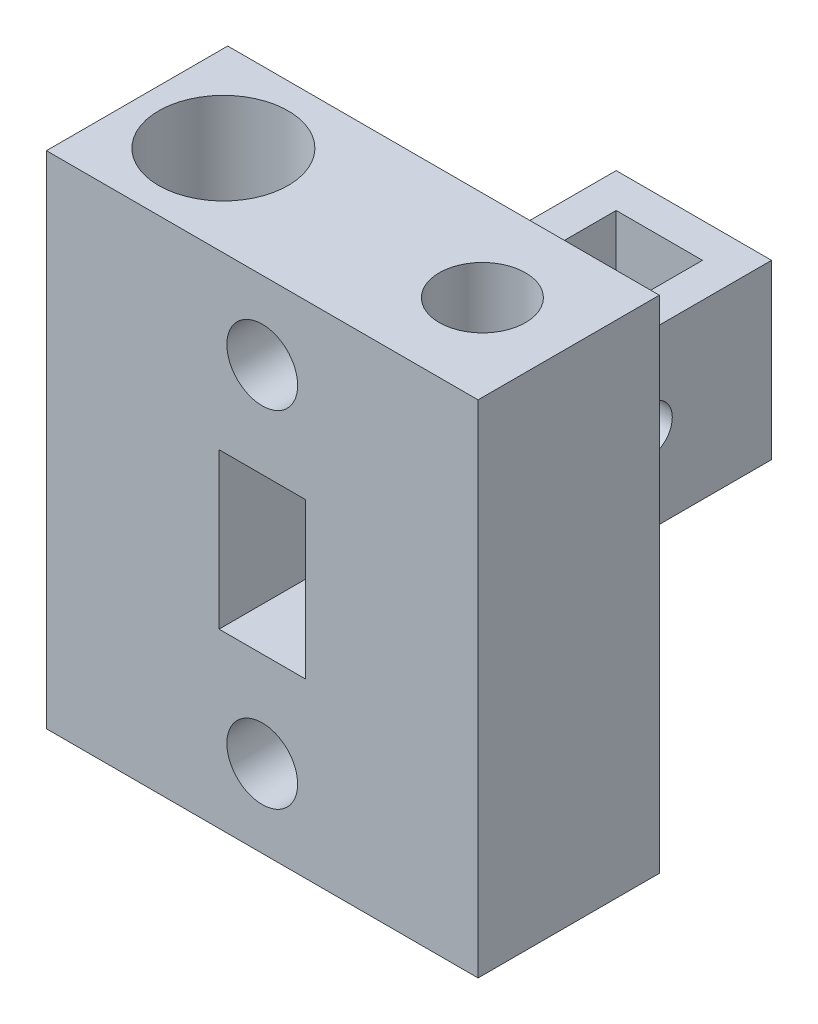
SolidWorks part; units mm, degrees
ref_plane "Front Plane" through (0, 0, 0) normal (0, 0, 1) x (1, 0, 0)
ref_plane "Top Plane" through (0, 0, 0) normal (0, 1, 0) x (1, 0, 0)
ref_plane "Right Plane" through (0, 0, 0) normal (1, 0, 0) x (0, 0, -1)
sketch "Sketch1" plane through (0, 0, 0) normal (0, 1, 0) x (1, 0, 0)
  line L1 (-25, 10.5) -> (25, 10.5)
  line L2 (-25, 10.5) -> (-25, -10.5)
  line L3 (-25, -10.5) -> (25, -10.5)
  line L4 (25, 10.5) -> (25, -10.5)
  line L5 (-25, 10.5) -> (25, -10.5) construction
  line L6 (-25, -10.5) -> (25, 10.5) construction
  point P0 (0, 0)
  dimension "D1" = 21
  dimension "D2" = 50
extrude "Boss-Extrude1" add sketch "Sketch1" along normal blind 58
sketch "Sketch3" plane through (0, 58, 0) normal (0, 1, 0) x (1, 0, 0)
  line L0 (-15, 0) -> (15, 0) construction
  circle A0 centre (-15, 0) radius 7.5
  dimension "D1" = 15
  dimension "D2" = 30
extrude "Cut-Extrude1" cut sketch "Sketch3" against normal blind 24 contours A0
sketch "Sketch4" plane through (0, 58, 0) normal (0, 1, 0) x (1, 0, 0)
  line L0 (-15, 0) -> (15, 0) construction
  circle A0 centre (15, 0) radius 5
  dimension "D1" = 10
extrude "Cut-Extrude2" cut sketch "Sketch4" against normal up to next
sketch "Sketch5" plane through (0, 0, 0) normal (0, -1, 0) x (1, 0, 0)
  circle A1 centre (-15, 0) radius 7.5
  circle A2 centre (-15, 0) radius 7.5
  dimension "D1" = 0
extrude "Cut-Extrude3" cut sketch "Sketch5" against normal blind 24
sketch "Sketch6" plane through (0, 0, 0) normal (0, -1, 0) x (1, 0, 0)
  circle A0 centre (-15, 0) radius 4.5
extrude "Cut-Extrude4" cut sketch "Sketch6" against normal up to next
sketch "Sketch7" plane through (0, 0, 10.5) normal (0, 0, 1) x (1, 0, 0)
  line L0 (0, 58) -> (0, 0) construction
  line L1 (-25, 58) -> (25, 58) construction
  line L2 (-25, 0) -> (25, 0) construction
  line L3 (-25, 29) -> (25, 29) construction
  line L4 (-25, 58) -> (-25, 0) construction
  line L5 (25, 58) -> (25, 0) construction
  circle A1 centre (0, 49) radius 4.1
  circle A2 centre (0, 9) radius 4.1
  point P24 (0, 9)
  dimension "D1" = 8.2
  dimension "D2" = 9
sketch "Sketch8" plane through (0, 0, 10.5) normal (0, 0, 1) x (1, 0, 0)
  line L0 (-25, 29) -> (25, 29) construction
  line L1 (-25, 58) -> (-25, 0) construction
  line L2 (25, 58) -> (25, 0) construction
  line L3 (0, 58) -> (0, 0) construction
  line L4 (-25, 58) -> (25, 58) construction
  line L6 (-5, 20) -> (5, 20)
  line L7 (-5, 20) -> (-5, 38)
  line L8 (-5, 38) -> (5, 38)
  line L9 (5, 20) -> (5, 38)
  line L10 (-5, 20) -> (5, 38) construction
  line L11 (-5, 38) -> (5, 20) construction
  point P11 (0, 29)
  dimension "D1" = 18
  dimension "D2" = 10
extrude "Cut-Extrude5" cut sketch "Sketch8" against normal up to next
sketch "Sketch10" plane through (0, 0, -10.5) normal (0, 0, -1) x (-1, 0, 0)
  line L0 (-25, 29) -> (25, 29) construction
  line L1 (-25, 58) -> (-25, 0) construction
  line L2 (25, 58) -> (25, 0) construction
  line L3 (0, 58) -> (0, 0) construction
  line L4 (-25, 58) -> (25, 58) construction
extrude "Cut-Extrude6" cut sketch "Sketch7" against normal blind 15
sketch "Sketch11" plane through (0, 0, -10.5) normal (0, 0, -1) x (-1, 0, 0)
  line L0 (-25, 29) -> (25, 29) construction
  line L1 (9, 39) -> (5, 39)
  line L2 (9, 39) -> (9, 19)
  line L3 (9, 19) -> (5, 19)
  line L4 (5, 39) -> (5, 19)
  line L5 (9, 39) -> (5, 19) construction
  line L6 (9, 19) -> (5, 39) construction
  line L7 (0, 58) -> (0, 0) construction
  line L8 (0, 58) -> (0, 0)
  line L9 (-9, 19) -> (-5, 19)
  line L10 (-5, 39) -> (-5, 19)
  line L11 (-9, 39) -> (-5, 39)
  line L12 (-9, 39) -> (-9, 19)
  point P0 (7, 29)
  line M7 (-5, 20) -> (-5, 38)
  line M9 (5, 38) -> (5, 20)
  dimension "D1" = 5
  dimension "D2" = 4
  dimension "D3" = 20
extrude "Boss-Extrude2" add sketch "Sketch11" along normal blind 25 contours L1 L4 L3 L2 M9 | L11 L12 L9 L10 M7 region at (-7, 29, -10.5) region at (7, 29, -10.5)
sketch "Sketch12" plane through (0, 0, -35.5) normal (0, 0, -1) x (-1, 0, 0)
  line L1 (9, 19) -> (-9, 19)
  line L2 (9, 19) -> (9, 39)
  line L3 (9, 39) -> (-9, 39)
  line L4 (-9, 19) -> (-9, 39)
extrude "Boss-Extrude3" add sketch "Sketch12" along normal blind 4
sketch "Sketch13" plane through (9, 0, 0) normal (1, 0, 0) x (0, 0, -1)
  line L3 (10.5, 29) -> (39.5, 29) construction
  line L4 (10.5, 39) -> (10.5, 19) construction
  line L5 (39.5, 39) -> (39.5, 19) construction
  line L6 (16.25, 29) -> (25.25, 29) construction
  line L7 (16.25, 31.75) -> (25.25, 31.75)
  line L8 (16.25, 26.25) -> (25.25, 26.25)
  arc A0 (16.25, 31.75) -> (16.25, 26.25) centre (16.25, 29) ccw
  arc A1 (25.25, 26.25) -> (25.25, 31.75) centre (25.25, 29) ccw
  point P1 (13.5, 29)
  point P14 (20.75, 29)
  dimension "D1" = 5.5
  dimension "D2" = 3
  dimension "D3" = 9
extrude "Cut-Extrude7" cut sketch "Sketch13" against normal through all
